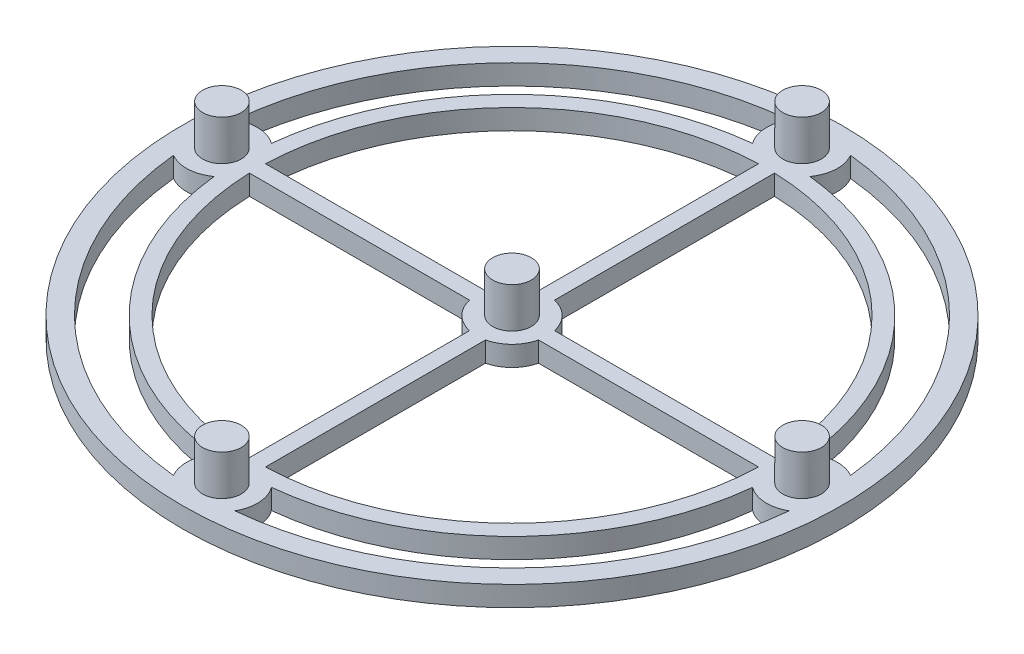
SolidWorks part; units mm, degrees
ref_plane "Front Plane" through (0, 0, 0) normal (0, 0, 1) x (1, 0, 0)
ref_plane "Top Plane" through (0, 0, 0) normal (0, 1, 0) x (1, 0, 0)
ref_plane "Right Plane" through (0, 0, 0) normal (1, 0, 0) x (0, 0, -1)
sketch "Sketch1" plane through (0, 0, 0) normal (0, 1, 0) x (1, 0, 0)
  line L0 (0, 0) -> (0, 72) construction
  circle A0 centre (0, 72) radius 4.8
  circle A1 centre (0, 0) radius 4.8
  circle A2 centre (72, 0) radius 4.8
  circle A3 centre (0, -72) radius 4.8
  circle A4 centre (-72, 0) radius 4.8
  circle A5 centre (0, 0) radius 76.8 construction
  dimension "D1" = 9.6
  dimension "D3" = 9.6
  dimension "D2" = 72
  dimension "D5" = 72
  dimension "D4" = 4
extrude "Boss-Extrude1" add sketch "Sketch1" along normal blind 15
sketch "Sketch2" plane through (0, 0, 0) normal (0, -1, 0) x (1, 0, 0)
  line L0 (0, 0) -> (0, 63.2) construction
  line L1 (-2, 8.5697) -> (-2, 63.1683)
  line L2 (2, 8.5697) -> (2, 63.1683)
  line L3 (8.5697, 2) -> (63.1683, 2)
  line L4 (8.5697, -2) -> (63.1683, -2)
  line L5 (2, -8.5697) -> (2, -63.1683)
  line L6 (-2, -8.5697) -> (-2, -63.1683)
  line L7 (-8.5697, -2) -> (-63.1683, -2)
  line L8 (-8.5697, 2) -> (-63.1683, 2)
  line L9 (0, 0) -> (2, 8.5697) construction
  arc A0 (76.4222, 7.6082) -> (66.8222, 7.1155) centre (72, 0) ccw
  arc A1 (-7.1155, 66.8222) -> (-66.8222, 7.1155) centre (0, 0) ccw
  circle A2 centre (0, 0) radius 81.8
  circle A3 centre (0, 0) radius 81.8
  circle A4 centre (0, 72) radius 4.8 construction
  arc A5 (66.8222, 7.1155) -> (7.1155, 66.8222) centre (0, 0) ccw
  arc A6 (-2, 63.1683) -> (-63.1683, 2) centre (0, 0) ccw
  circle A7 centre (0, 0) radius 8.8
  arc A8 (-2, 8.5697) -> (-8.5697, 2) centre (0, 0) ccw
  arc A9 (8.5697, 2) -> (2, 8.5697) centre (0, 0) ccw
  circle A10 centre (0, 0) radius 63.2 construction
  arc A11 (63.1683, 2) -> (2, 63.1683) centre (0, 0) ccw
  arc A12 (2, -63.1683) -> (63.1683, -2) centre (0, 0) ccw
  arc A13 (2, -8.5697) -> (8.5697, -2) centre (0, 0) ccw
  arc A14 (-8.5697, -2) -> (-2, -8.5697) centre (0, 0) ccw
  arc A15 (-63.1683, -2) -> (-2, -63.1683) centre (0, 0) ccw
  arc A16 (7.1155, 66.8222) -> (7.6082, 76.4222) centre (0, 72) ccw
  arc A17 (76.4222, 7.6082) -> (7.6082, 76.4222) centre (0, 0) ccw
  arc A18 (7.6082, -76.4222) -> (7.1155, -66.8222) centre (0, -72) ccw
  arc A19 (7.1155, -66.8222) -> (66.8222, -7.1155) centre (0, 0) ccw
  arc A20 (66.8222, -7.1155) -> (76.4222, -7.6082) centre (72, 0) ccw
  circle A21 centre (-72, 0) radius 4.8 construction
  circle A23 centre (0, 0) radius 76.8 construction
  circle A24 centre (0, 72) radius 8.8
  arc A25 (-7.6082, 76.4222) -> (-7.1155, 66.8222) centre (0, 72) ccw
  arc A26 (-7.6082, 76.4222) -> (-76.4222, 7.6082) centre (0, 0) ccw
  arc A27 (-66.8222, 7.1155) -> (-76.4222, 7.6082) centre (-72, 0) ccw
  circle A28 centre (0, 0) radius 67.2 construction
  arc A29 (7.6082, -76.4222) -> (76.4222, -7.6082) centre (0, 0) ccw
  arc A30 (-76.4222, -7.6082) -> (-66.8222, -7.1155) centre (-72, 0) ccw
  arc A31 (-66.8222, -7.1155) -> (-7.1155, -66.8222) centre (0, 0) ccw
  arc A32 (-7.1155, -66.8222) -> (-7.6082, -76.4222) centre (0, -72) ccw
  arc A33 (-76.4222, -7.6082) -> (-7.6082, -76.4222) centre (0, 0) ccw
  point P17 (63.2, 0)
  point P32 (64.2637, 19.6474)
  point P61 (0, 0)
  dimension "D6" = 4
  dimension "D4" = 4
  dimension "D1" = 5
  dimension "D2" = 4
  dimension "D3" = 4
  dimension "D7" = 4
  dimension "D5" = 4
  dimension "D8" = 4
extrude "Boss-Extrude2" add sketch "Sketch2" against normal blind 5
equation "\"Modulus\"= 3mm"
equation "\"Sun\"= 32"
equation "\"Planet\"= 16"
equation "\"Ring\"= 64"
equation "\"Sun Radius\"= \"Sun\" * \"Modulus\" / 2"
equation "\"Planet Radius\"= \"Planet\" * \"Modulus\" / 2"
equation "\"Ring Radius\"= \"Ring\" * \"Modulus\" / 2"
equation "\"D2@Sketch1\"=\"Sun Radius\" + \"Planet Radius\""
